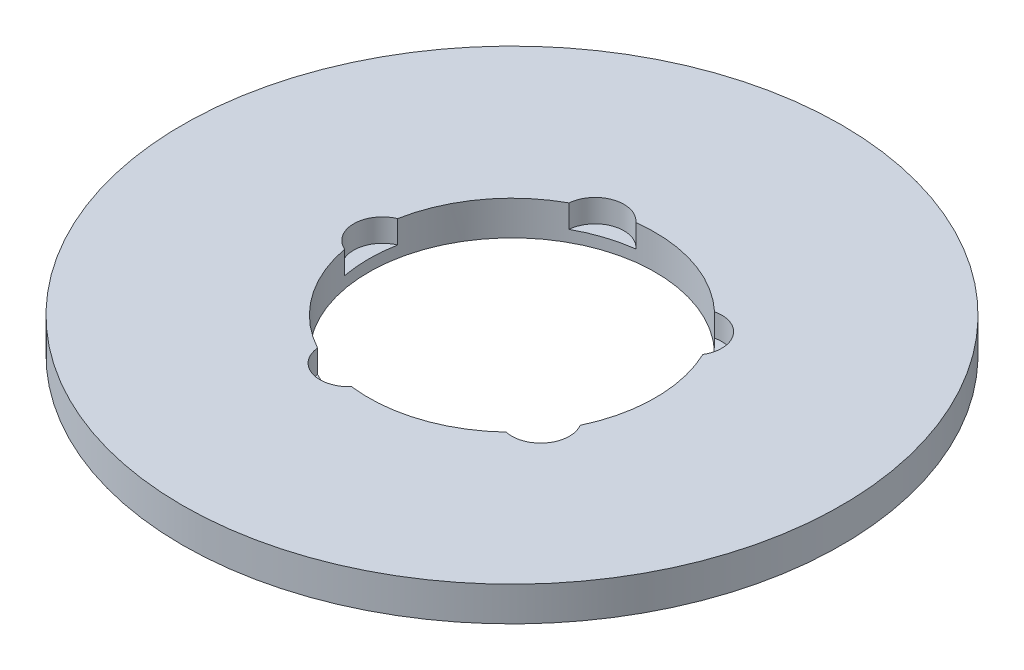
SolidWorks part; units mm, degrees
ref_plane "Front Plane" through (0, 0, 0) normal (0, 0, 1) x (1, 0, 0)
ref_plane "Top Plane" through (0, 0, 0) normal (0, 1, 0) x (1, 0, 0)
ref_plane "Right Plane" through (0, 0, 0) normal (1, 0, 0) x (0, 0, -1)
sketch "Sketch1" plane through (0, 0, 0) normal (0, 1, 0) x (1, 0, 0)
  circle A0 centre (0, 0) radius 57.5
  dimension "FLANGE_OD" = 115
extrude "Boss-Extrude1" add sketch "Sketch1" along normal blind 6
sketch "Sketch2" plane through (0, 0, 0) normal (0, 1, 0) x (1, 0, 0)
  circle A0 centre (0, 0) radius 25
  dimension "BORE_D" = 50
extrude "Cut-Extrude1" cut sketch "Sketch2" along normal through all
sketch "Sketch3" plane through (0, 6, 0) normal (0, 1, 0) x (1, 0, 0)
  circle A0 centre (0, 0) radius 22.5953 construction
  circle A1 centre (-22.5953, 0) radius 5.0279
  dimension "BOLT_D" = 10.0558
  dimension "BOLT_PCD" = 45.1907
extrude "Cut-Extrude2" cut sketch "Sketch3" against normal blind 3.9951
pattern_circular "CirPattern1" count 5 over 360 about axis through (0, 0, 0) along (0, 1, 0) of "Cut-Extrude2"
